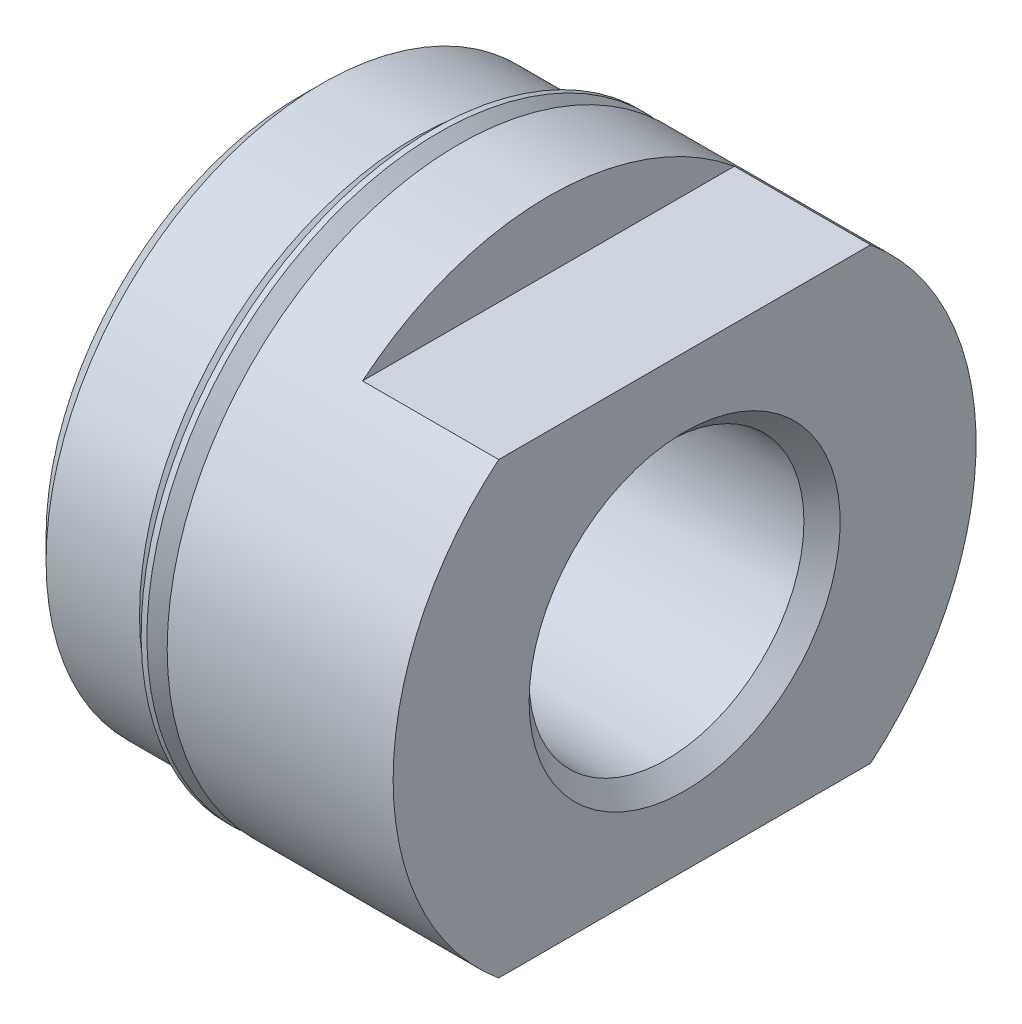
SolidWorks part; units mm, degrees
material "AISI 304"
ref_plane "Front Plane" through (0, 0, 0) normal (0, 0, 1) x (1, 0, 0)
ref_plane "Top Plane" through (0, 0, 0) normal (0, 1, 0) x (1, 0, 0)
ref_plane "Right Plane" through (0, 0, 0) normal (1, 0, 0) x (0, 0, -1)
sketch "Sketch1" plane through (0, 0, 0) normal (0, 0, 1) x (1, 0, 0)
  line L0 (0, 0) -> (0, 8.9091)
  line L1 (0, 8.9091) -> (0.762, 9.671)
  line L2 (0.762, 9.671) -> (4.0386, 9.671)
  line L3 (4.0386, 9.671) -> (4.8006, 8.9091)
  line L4 (4.8006, 8.9091) -> (5.5626, 8.9091)
  line L5 (5.5626, 8.9091) -> (5.5626, 10.2235)
  line L6 (5.5626, 10.2235) -> (13.4874, 10.2235)
  line L7 (13.4874, 10.2235) -> (13.4874, 0)
  line L8 (13.4874, 0) -> (0, 0)
  line L9 (13.4874, 0) -> (0, 0) construction
revolve "Revolve1" add sketch "Sketch1" angle 360 about L9 reverse direction yes
sketch "Sketch2" plane through (0, 0, 0) normal (0, 0, 1) x (1, 0, 0)
  line L0 (0, 0) -> (0, 4.3688)
  line L1 (0, 4.3688) -> (-1.5889, 4.3688)
  line L2 (-1.5889, 4.3688) -> (12.8524, 4.8197)
  line L3 (12.8524, 4.8197) -> (13.4874, 5.4547)
  line L4 (13.4874, 5.4547) -> (13.4874, 0)
  line L5 (13.4874, 0) -> (0, 0)
  line L6 (13.4874, 0) -> (0, 0) construction
revolve "Cut-Revolve1" cut sketch "Sketch2" angle 360 about L6 reverse direction yes
cosmetic thread "Cosmetic Thread1" parameters "D1"=7.6708, "D2"=10.287
ref_plane "Plane1" through (13.4874, 0, 0) normal (1, 0, 0) x (0, 0, -1)
sketch "Sketch3" plane through (13.4874, 0, 0) normal (1, 0, 0) x (0, 0, -1)
  line L0 (-40.894, 20.447) -> (-40.894, -20.447)
  line L1 (-40.894, -20.447) -> (40.894, -20.447)
  line L2 (40.894, -20.447) -> (40.894, 20.447)
  line L3 (40.894, 20.447) -> (-40.894, 20.447)
  line L4 (-20.447, 7.874) -> (-20.447, -7.874)
  line L5 (-20.447, -7.874) -> (20.447, -7.874)
  line L6 (20.447, -7.874) -> (20.447, 7.874)
  line L7 (20.447, 7.874) -> (-20.447, 7.874)
extrude "Cut-Extrude1" cut sketch "Sketch3" against normal blind 4.7752
ref_plane "Plane2" through (24.6126, 0, 0) normal (1, 0, 0) x (0, 0, -1)
ref_plane "Plane3" through (0, 0, 0) normal (0, 0.9998, 0.0175) x (1, 0, 0)
ref_plane "Plane4" through (17.4752, 0, 0) normal (1, 0, 0) x (0, 0, -1)
ref_plane "Plane5" through (4.8006, 0, 0) normal (1, 0, 0) x (0, 0, -1)
sketch "Sketch4" plane through (0, 0, 0) normal (0, 0, 1) x (1, 0, 0)
  line L0 (4.6479, 10.1393) -> (5.4401, 9.3472)
  line L1 (5.4401, 9.1676) -> (5.1816, 8.9091)
  line L2 (5.1816, 8.9091) -> (4.8006, 8.9091)
  line L3 (4.8006, 8.9091) -> (4.8006, 8.6551)
  line L4 (4.8006, 8.6551) -> (5.5626, 8.655)
  line L5 (5.5626, 8.655) -> (5.5626, 9.512)
  line L6 (5.5626, 9.512) -> (4.8511, 10.2235)
  line L7 (4.8511, 10.2235) -> (4.6479, 10.2235)
  line L8 (4.6479, 10.2235) -> (4.6479, 10.1393)
  line L9 (5.5626, 0) -> (4.8006, 0) construction
  arc A0 (5.4401, 9.3472) -> (5.4401, 9.1676) centre (5.3503, 9.2574) cw
revolve "Revolve2" add sketch "Sketch4" angle 360 about L9 reverse direction yes
ref_plane "Plane6" through (13.6144, 0, 0) normal (1, 0, 0) x (0, 0, -1)
ref_plane "Plane7" through (0, 0, 0) normal (1, 0, 0) x (0, 0, -1)
ref_plane "Plane8" through (8.7122, 0, 0) normal (1, 0, 0) x (0, 0, -1)
ref_plane "Plane9" through (13.4874, 0, 0) normal (1, 0, 0) x (0, 0, -1)
ref_plane "Plane10" through (0, 0, 0) normal (0, 0, 1) x (1, 0, 0)
ref_plane "Plane11" through (0, 0, 0) normal (0, 1, 0) x (1, 0, 0)
ref_plane "Plane12" through (0, 2.032, 0) normal (0, 1, 0) x (1, 0, 0)
ref_plane "Plane13" through (24.6126, 0, 0) normal (1, 0, 0) x (0, 0, -1)
ref_plane "cut1 XY" through (13.4874, 0, 0) normal (1, 0, 0) x (0, 0, -1)
ref_plane "cut1 XZ" through (0, 7.874, 0) normal (0, -1, 0) x (-1, 0, 0)
ref_plane "cut1 YZ" through (0, 0, 0) normal (0, 0, -1) x (-1, 0, 0)
ref_axis "cut1 X" through (13.4874, 7.874, 80.9) along (0, 0, -1)
ref_axis "cut1 Y" through (13.4874, -50, 0) along (0, 1, 0)
ref_axis "cut1 Z" through (80.9, 7.874, 0) along (-1, 0, 0)
sketch3d "cut1"
  point P0 (13.4874, 7.874, 0)
ref_plane "cut2 XY" through (13.4874, 0, 0) normal (1, 0, 0) x (0, 0, -1)
ref_plane "cut2 XZ" through (0, -7.874, 0) normal (0, -1, 0) x (-1, 0, 0)
ref_plane "cut2 YZ" through (0, 0, 0) normal (0, 0, -1) x (-1, 0, 0)
ref_axis "cut2 X" through (13.4874, -7.874, 80.9) along (0, 0, -1)
ref_axis "cut2 Y" through (13.4874, -50, 0) along (0, 1, 0)
ref_axis "cut2 Z" through (80.9, -7.874, 0) along (-1, 0, 0)
sketch3d "cut2"
  point P0 (13.4874, -7.874, 0)
ref_plane "cutf1 XY" through (0, 0, 0) normal (0, 0, 1) x (1, 0, 0)
ref_plane "cutf1 XZ" through (0, 0, 0) normal (0, -1, 0) x (-1, 0, 0)
ref_plane "cutf1 YZ" through (13.4874, 0, 0) normal (1, 0, 0) x (0, 0, -1)
ref_axis "cutf1 X" through (-80.9, 0, 0) along (1, 0, 0)
ref_axis "cutf1 Y" through (13.4874, -50, 0) along (0, 1, 0)
ref_axis "cutf1 Z" through (13.4874, 0, 80.9) along (0, 0, -1)
sketch3d "cutf1"
  point P0 (13.4874, 0, 0)
ref_plane "cutf2 XY" through (0, 0, 0) normal (0, 0, 1) x (1, 0, 0)
ref_plane "cutf2 XZ" through (0, 0, 0) normal (0, -1, 0) x (-1, 0, 0)
ref_plane "cutf2 YZ" through (8.7122, 0, 0) normal (1, 0, 0) x (0, 0, -1)
ref_axis "cutf2 X" through (-80.9, 0, 0) along (1, 0, 0)
ref_axis "cutf2 Y" through (8.7122, -50, 0) along (0, 1, 0)
ref_axis "cutf2 Z" through (8.7122, 0, 80.9) along (0, 0, -1)
sketch3d "cutf2"
  point P0 (8.7122, 0, 0)
ref_plane "lovra XY" through (13.4874, 0, 0) normal (1, 0, 0) x (0, 0, -1)
ref_plane "lovra XZ" through (0, 0, 0) normal (0, 0, -1) x (-1, 0, 0)
ref_plane "lovra YZ" through (0, 0, 0) normal (0, 1, 0) x (1, 0, 0)
ref_axis "lovra X" through (13.4874, -50, 0) along (0, 1, 0)
ref_axis "lovra Y" through (13.4874, 0, -80.9) along (0, 0, 1)
ref_axis "lovra Z" through (80.9, 0, 0) along (-1, 0, 0)
sketch3d "lovra"
  point P0 (13.4874, 0, 0)
ref_plane "lovra1 XY" through (8.7122, 0, 0) normal (1, 0, 0) x (0, 0, -1)
ref_plane "lovra1 XZ" through (0, 0, 0) normal (0, -1, 0) x (-1, 0, 0)
ref_plane "lovra1 YZ" through (0, 0, 0) normal (0, 0, -1) x (-1, 0, 0)
ref_axis "lovra1 X" through (8.7122, 0, 80.9) along (0, 0, -1)
ref_axis "lovra1 Y" through (8.7122, -50, 0) along (0, 1, 0)
ref_axis "lovra1 Z" through (80.9, 0, 0) along (-1, 0, 0)
sketch3d "lovra1"
  point P0 (8.7122, 0, 0)
ref_plane "lovra2 XY" through (8.7122, 0, 0) normal (1, 0, 0) x (0, 0, -1)
ref_plane "lovra2 XZ" through (0, 7.874, 0) normal (0, -1, 0) x (-1, 0, 0)
ref_plane "lovra2 YZ" through (0, 0, 0) normal (0, 0, -1) x (-1, 0, 0)
ref_axis "lovra2 X" through (8.7122, 7.874, 80.9) along (0, 0, -1)
ref_axis "lovra2 Y" through (8.7122, -50, 0) along (0, 1, 0)
ref_axis "lovra2 Z" through (80.9, 7.874, 0) along (-1, 0, 0)
sketch3d "lovra2"
  point P0 (8.7122, 7.874, 0)
ref_plane "lovra21 XY" through (0, 0, 0) normal (1, 0, 0) x (0, 0, -1)
ref_plane "lovra21 XZ" through (0, 0, 0) normal (0, -1, 0) x (-1, 0, 0)
ref_plane "lovra21 YZ" through (0, 0, 5.2705) normal (0, 0, -1) x (-1, 0, 0)
ref_axis "lovra21 X" through (0, 0, 80.9) along (0, 0, -1)
ref_axis "lovra21 Y" through (0, -50, 5.2705) along (0, 1, 0)
ref_axis "lovra21 Z" through (80.9, 0, 5.2705) along (-1, 0, 0)
sketch3d "lovra21"
  point P0 (0, 0, 5.2705)
ref_plane "lovra22 XY" through (0, 0, 0) normal (1, 0, 0) x (0, 0, -1)
ref_plane "lovra22 XZ" through (0, 0, 0) normal (0, -1, 0) x (-1, 0, 0)
ref_plane "lovra22 YZ" through (0, 0, -5.2705) normal (0, 0, -1) x (-1, 0, 0)
ref_axis "lovra22 X" through (0, 0, 80.9) along (0, 0, -1)
ref_axis "lovra22 Y" through (0, -50, -5.2705) along (0, 1, 0)
ref_axis "lovra22 Z" through (80.9, 0, -5.2705) along (-1, 0, 0)
sketch3d "lovra22"
  point P0 (0, 0, -5.2705)
ref_plane "lovra3 XY" through (8.7122, 0, 0) normal (1, 0, 0) x (0, 0, -1)
ref_plane "lovra3 XZ" through (0, -7.874, 0) normal (0, -1, 0) x (-1, 0, 0)
ref_plane "lovra3 YZ" through (0, 0, 0) normal (0, 0, -1) x (-1, 0, 0)
ref_axis "lovra3 X" through (8.7122, -7.874, 80.9) along (0, 0, -1)
ref_axis "lovra3 Y" through (8.7122, -50, 0) along (0, 1, 0)
ref_axis "lovra3 Z" through (80.9, -7.874, 0) along (-1, 0, 0)
sketch3d "lovra3"
  point P0 (8.7122, -7.874, 0)
ref_plane "olen XY" through (13.4874, 0, 0) normal (1, 0, 0) x (0, 0, -1)
ref_plane "olen XZ" through (0, 0, 0) normal (0, -1, 0) x (-1, 0, 0)
ref_plane "olen YZ" through (0, 0, 0) normal (0, 0, -1) x (-1, 0, 0)
ref_axis "olen X" through (13.4874, 0, 80.9) along (0, 0, -1)
ref_axis "olen Y" through (13.4874, -50, 0) along (0, 1, 0)
ref_axis "olen Z" through (80.9, 0, 0) along (-1, 0, 0)
sketch3d "olen"
  point P0 (13.4874, 0, 0)
ref_plane "to_mounting_bracket XY" through (24.6126, 0, 0) normal (1, 0, 0) x (0, 0, -1)
ref_plane "to_mounting_bracket XZ" through (0, 0, 0) normal (0, -1, 0) x (-1, 0, 0)
ref_plane "to_mounting_bracket YZ" through (0, 0, 0) normal (0, 0, -1) x (-1, 0, 0)
ref_axis "to_mounting_bracket X" through (24.6126, 0, 80.9) along (0, 0, -1)
ref_axis "to_mounting_bracket Y" through (24.6126, -50, 0) along (0, 1, 0)
ref_axis "to_mounting_bracket Z" through (80.9, 0, 0) along (-1, 0, 0)
sketch3d "to_mounting_bracket"
  point P0 (24.6126, 0, 0)
ref_plane "to_nut XY" through (0, 0, 0) normal (1, 0, 0) x (0, 0, -1)
ref_plane "to_nut XZ" through (0, 0, 0) normal (0, -1, 0) x (-1, 0, 0)
ref_plane "to_nut YZ" through (0, 0, 0) normal (0, 0, -1) x (-1, 0, 0)
ref_axis "to_nut X" through (0, 0, 80.9) along (0, 0, -1)
ref_axis "to_nut Y" through (0, -50, 0) along (0, 1, 0)
ref_axis "to_nut Z" through (80.9, 0, 0) along (-1, 0, 0)
sketch3d "to_nut"
  point P0 (0, 0, 0)
ref_plane "to_pin XY" through (0, 0, 0) normal (0, 0, 1) x (1, 0, 0)
ref_plane "to_pin XZ" through (0, 0, 0) normal (0, -1, 0) x (-1, 0, 0)
ref_plane "to_pin YZ" through (33.3248, 0, 0) normal (1, 0, 0) x (0, 0, -1)
ref_axis "to_pin X" through (-80.9, 0, 0) along (1, 0, 0)
ref_axis "to_pin Y" through (33.3248, -50, 0) along (0, 1, 0)
ref_axis "to_pin Z" through (33.3248, 0, 80.9) along (0, 0, -1)
sketch3d "to_pin"
  point P0 (33.3248, 0, 0)
ref_plane "to_screw XY" through (0, 2.032, 0) normal (0, 1, 0) x (1, 0, 0)
ref_plane "to_screw XZ" through (0, 0, -6.0452) normal (0, 0, 1) x (1, 0, 0)
ref_plane "to_screw YZ" through (17.4752, 0, 0) normal (1, 0, 0) x (0, 0, -1)
ref_axis "to_screw X" through (-80.9, 2.032, -6.0452) along (1, 0, 0)
ref_axis "to_screw Y" through (17.4752, 2.032, 50) along (0, 0, -1)
ref_axis "to_screw Z" through (17.4752, 50, -6.0452) along (0, -1, 0)
sketch3d "to_screw"
  point P0 (17.4752, 2.032, -6.0452)
ref_plane "to_tube XY" through (4.8006, 0, 0) normal (1, 0, 0) x (0, 0, -1)
ref_plane "to_tube XZ" through (0, 0, 0) normal (0, -1, 0) x (-1, 0, 0)
ref_plane "to_tube YZ" through (0, 0, 0) normal (0, 0, -1) x (-1, 0, 0)
ref_axis "to_tube X" through (4.8006, 0, 80.9) along (0, 0, -1)
ref_axis "to_tube Y" through (4.8006, -50, 0) along (0, 1, 0)
ref_axis "to_tube Z" through (80.9, 0, 0) along (-1, 0, 0)
sketch3d "to_tube"
  point P0 (4.8006, 0, 0)
